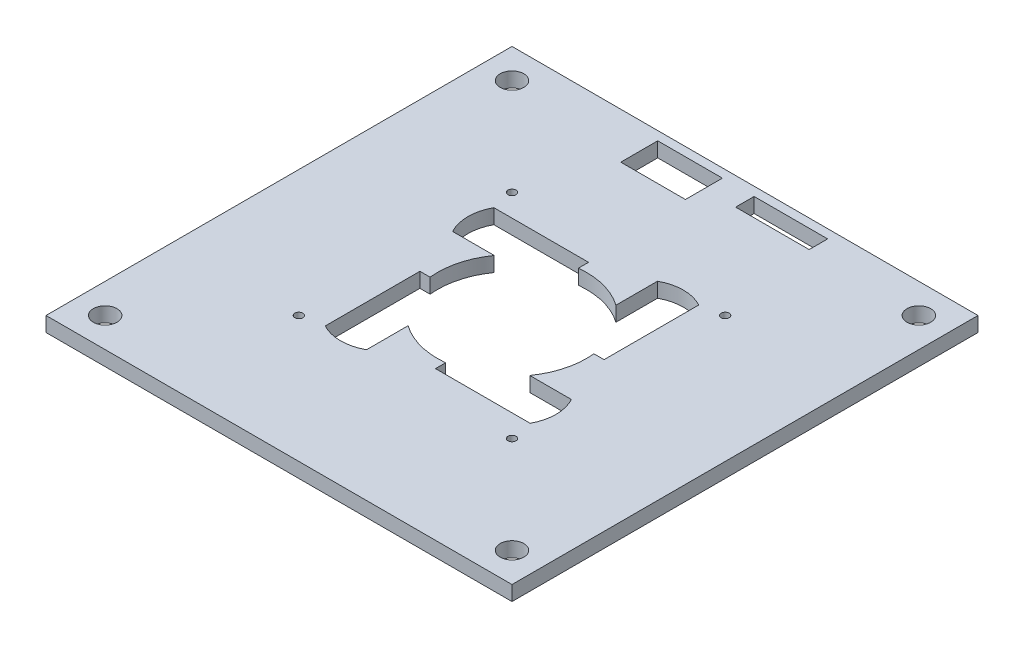
SolidWorks part; units mm, degrees
ref_plane "Front Plane" through (0, 0, 0) normal (0, 0, 1) x (1, 0, 0)
ref_plane "Top Plane" through (0, 0, 0) normal (0, 1, 0) x (1, 0, 0)
ref_plane "Right Plane" through (0, 0, 0) normal (1, 0, 0) x (0, 0, -1)
sketch "Sketch1" plane through (0, 0, 0) normal (0, 1, 0) x (1, 0, 0)
  line L0 (-100.0125, 100.0125) -> (-87.3125, 100.0125) construction
  line L1 (-100.0125, -100.0125) -> (100.0125, -100.0125)
  line L2 (-100.0125, -100.0125) -> (-100.0125, 100.0125)
  line L3 (-100.0125, 100.0125) -> (100.0125, 100.0125)
  line L4 (100.0125, -100.0125) -> (100.0125, 100.0125)
  line L5 (-100.0125, -100.0125) -> (100.0125, 100.0125) construction
  line L6 (-100.0125, 100.0125) -> (100.0125, -100.0125) construction
  line L7 (-74.6125, -74.6125) -> (74.6125, -74.6125) construction
  line L8 (-74.6125, -74.6125) -> (-74.6125, 74.6125) construction
  line L9 (-74.6125, 74.6125) -> (74.6125, 74.6125) construction
  line L10 (74.6125, -74.6125) -> (74.6125, 74.6125) construction
  line L11 (-74.6125, -74.6125) -> (74.6125, 74.6125) construction
  line L12 (-74.6125, 74.6125) -> (74.6125, -74.6125) construction
  line L13 (-87.3125, 100.0125) -> (-87.3125, -100.0125) construction
  line L14 (0, -55) -> (0, 55) construction
  line L15 (-55, 0) -> (55, 0) construction
  line L16 (-100.0125, 96.2025) -> (100.0125, 96.2025) construction
  line L17 (-45.75, 45.75) -> (45.75, -45.75) construction
  line L18 (-33.6459, 96.2025) -> (-5.887, 96.2025)
  line L19 (-33.6459, 96.2025) -> (-33.6459, 80.3284)
  line L20 (-33.6459, 80.3284) -> (-5.887, 80.3284)
  line L21 (-5.887, 96.2025) -> (-5.887, 80.3284)
  line L22 (7.7239, 96.2025) -> (39.2871, 96.2025)
  line L23 (7.7239, 96.2025) -> (7.7239, 88.2654)
  line L24 (7.7239, 88.2654) -> (39.2871, 88.2654)
  line L25 (39.2871, 96.2025) -> (39.2871, 88.2654)
  line L26 (45.75, 45.75) -> (-45.75, -45.75) construction
  line L27 (36.332, -29.0597) -> (36.332, -25.6135) construction
  line L28 (10.332, -35.1866) -> (18.332, -35.1866) construction
  line L29 (18.332, -19.4866) -> (10.332, -19.4866) construction
  line L30 (4.332, -32.1866) -> (4.332, -22.4866) construction
  line L31 (40.332, -35.1866) -> (4.332, -35.1866) construction
  line L32 (4.332, -35.1866) -> (4.332, -19.4866) construction
  line L33 (4.332, -19.4866) -> (40.332, -19.4866) construction
  line L34 (43.972, -36.1866) -> (3.332, -36.1866)
  line L35 (3.332, -36.1866) -> (3.332, -31.8261)
  line L36 (26.1199, -18.4866) -> (43.972, -18.4866)
  line L37 (-18.4866, -26.1199) -> (-18.4866, -43.972)
  line L38 (-36.1866, -3.332) -> (-31.8261, -3.332)
  line L39 (-36.1866, -43.972) -> (-36.1866, -3.332)
  line L40 (-26.1199, 18.4866) -> (-43.972, 18.4866)
  line L41 (-3.332, 36.1866) -> (-3.332, 31.8261)
  line L42 (-43.972, 36.1866) -> (-3.332, 36.1866)
  line L44 (36.1866, 3.332) -> (31.8261, 3.332)
  line L45 (36.1866, 43.972) -> (36.1866, 3.332)
  line L46 (18.4866, 26.1199) -> (18.4866, 43.972)
  circle A0 centre (-87.3125, 87.3125) radius 5.08
  circle A1 centre (87.3125, 87.3125) radius 5.08
  circle A2 centre (-87.3125, -87.3125) radius 5.08
  circle A3 centre (87.3125, -87.3125) radius 5.08
  circle A4 centre (45.75, -45.75) radius 1.7272
  circle A5 centre (-45.75, -45.75) radius 1.7272
  circle A6 centre (45.75, 45.75) radius 1.7272
  circle A7 centre (-45.75, 45.75) radius 1.7272
  arc A8 (-26.1199, 18.4866) -> (-31.8261, -3.332) centre (0, 0) ccw
  arc A9 (40.332, -19.4866) -> (40.332, -35.1866) centre (24.6914, -27.3366) cw construction
  arc A10 (43.972, -18.4866) -> (43.972, -36.1866) centre (27.7262, -27.3366) cw
  arc A11 (-18.4866, -43.972) -> (-36.1866, -43.972) centre (-27.3366, -27.7262) cw
  arc A12 (-43.972, 18.4866) -> (-43.972, 36.1866) centre (-27.7262, 27.3366) cw
  arc A13 (18.4866, 43.972) -> (36.1866, 43.972) centre (27.3366, 27.7262) cw
  arc A14 (18.4866, 26.1199) -> (-3.332, 31.8261) centre (0, 0) ccw
  arc A15 (-18.4866, -26.1199) -> (3.332, -31.8261) centre (0, 0) ccw
  arc A16 (26.1199, -18.4866) -> (31.8261, 3.332) centre (0, 0) ccw
  point P0 (0, 0)
  point P6 (0, 0)
  point P11 (-87.3125, 87.3125)
  point P44 (0, 0)
  point P72 (0, 0)
  point P84 (0, 0)
  point P85 (0, 0)
  dimension "D5" = 10.16
  dimension "D7" = 64.0001
  dimension "D8" = 17.5
  dimension "D1" = 200.025
  dimension "D2" = 200.025
  dimension "D3" = 149.225
  dimension "D4" = 12.7
  dimension "D6" = 3.81
  dimension "D9" = 36
  dimension "D10" = 40.64
  dimension "D11" = 40.64
  dimension "D12" = 40.64
  dimension "D13" = 40.64
extrude "Boss-Extrude1" add sketch "Sketch1" along normal blind 6.35
sketch "Sketch2" plane through (0, 6.35, 0) normal (0, 1, 0) x (1, 0, 0)
  line L0 (-100.0125, -100.0125) -> (100.0125, -100.0125)
  line L1 (-100.0125, -100.0125) -> (-100.0125, 100.0125)
  line L2 (-100.0125, 100.0125) -> (100.0125, 100.0125)
  line L3 (100.0125, -100.0125) -> (100.0125, 100.0125)
  line L4 (-74.6125, -74.6125) -> (74.6125, -74.6125)
  line L5 (-74.6125, -74.6125) -> (-74.6125, 74.6125)
  line L6 (-74.6125, 74.6125) -> (74.6125, 74.6125)
  line L7 (74.6125, -74.6125) -> (74.6125, 74.6125)
  line L8 (-33.6459, 96.2025) -> (-5.887, 96.2025)
  line L9 (-33.6459, 96.2025) -> (-33.6459, 80.3284)
  line L10 (-33.6459, 80.3284) -> (-5.887, 80.3284)
  line L11 (-5.887, 96.2025) -> (-5.887, 80.3284)
  line L12 (7.7239, 96.2025) -> (39.2871, 96.2025)
  line L13 (7.7239, 96.2025) -> (7.7239, 88.2654)
  line L14 (7.7239, 88.2654) -> (39.2871, 88.2654)
  line L15 (39.2871, 96.2025) -> (39.2871, 88.2654)
  circle A0 centre (-87.3125, 87.3125) radius 5.08
  circle A1 centre (87.3125, 87.3125) radius 5.08
  circle A2 centre (-87.3125, -87.3125) radius 5.08
  circle A3 centre (87.3125, -87.3125) radius 5.08
extrude "Boss-Extrude2" add sketch "Sketch2" against normal blind 6.3503
